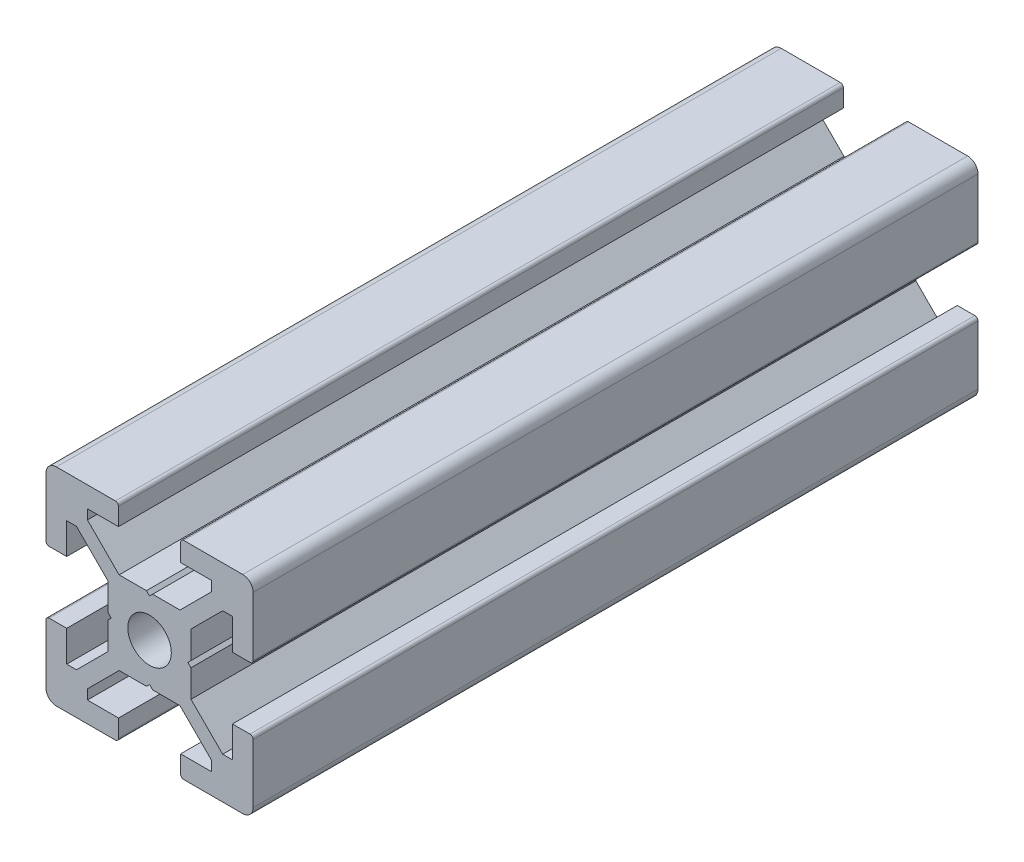
SolidWorks part; units mm, degrees
ref_plane "Front Plane" through (0, 0, 0) normal (0, 0, 1) x (1, 0, 0)
ref_plane "Top Plane" through (0, 0, 0) normal (0, 1, 0) x (1, 0, 0)
ref_plane "Right Plane" through (0, 0, 0) normal (1, 0, 0) x (0, 0, -1)
sketch "Sketch1" plane through (0, 0, 0) normal (0, 0, -1) x (-1, 0, 0)
  line L0 (10, 3.3) -> (10, 9)
  line L1 (9, 10) -> (3.3, 10)
  line L2 (3, 9.7) -> (3, 8)
  line L3 (3, 8) -> (6, 8)
  line L4 (6, 8) -> (6, 7.0607)
  line L5 (6, 7.0607) -> (2.9393, 4)
  line L6 (2.9393, 4) -> (0.3, 4)
  line L7 (0.3, 4) -> (0, 3.7)
  line L8 (0, 3.7) -> (-0.3, 4)
  line L9 (-0.3, 4) -> (-2.9393, 4)
  line L10 (-2.9393, 4) -> (-6, 7.0607)
  line L11 (-6, 7.0607) -> (-6, 8)
  line L12 (-6, 8) -> (-3, 8)
  line L13 (-3, 8) -> (-3, 9.7)
  line L14 (-3.3, 10) -> (-9, 10)
  line L15 (-10, 9) -> (-10, 3.3)
  line L16 (-9.7, 3) -> (-8, 3)
  line L17 (-8, 3) -> (-8, 6)
  line L18 (-8, 6) -> (-7.0607, 6)
  line L19 (-7.0607, 6) -> (-4, 2.9393)
  line L20 (-4, 2.9393) -> (-4, 0.3)
  line L21 (-4, 0.3) -> (-3.7, 0)
  line L22 (-3.7, 0) -> (-4, -0.3)
  line L23 (-4, -0.3) -> (-4, -2.9393)
  line L24 (-4, -2.9393) -> (-7.0607, -6)
  line L25 (-7.0607, -6) -> (-8, -6)
  line L26 (-8, -6) -> (-8, -3)
  line L27 (-8, -3) -> (-9.7, -3)
  line L28 (-10, -3.3) -> (-10, -9)
  line L29 (-9, -10) -> (-3.3, -10)
  line L30 (-3, -9.7) -> (-3, -8)
  line L31 (-3, -8) -> (-6, -8)
  line L32 (-6, -8) -> (-6, -7.0607)
  line L33 (-6, -7.0607) -> (-2.9393, -4)
  line L34 (-2.9393, -4) -> (-0.3, -4)
  line L35 (-0.3, -4) -> (0, -3.7)
  line L36 (0, -3.7) -> (0.3, -4)
  line L37 (0.3, -4) -> (2.9393, -4)
  line L38 (2.9393, -4) -> (6, -7.0607)
  line L39 (6, -7.0607) -> (6, -8)
  line L40 (6, -8) -> (3, -8)
  line L41 (3, -8) -> (3, -9.7)
  line L42 (3.3, -10) -> (9, -10)
  line L43 (10, -9) -> (10, -3.3)
  line L44 (9.7, -3) -> (8, -3)
  line L45 (8, -3) -> (8, -6)
  line L46 (8, -6) -> (7.0607, -6)
  line L47 (7.0607, -6) -> (4, -2.9393)
  line L48 (4, -2.9393) -> (4, -0.3)
  line L49 (4, -0.3) -> (3.7, 0)
  line L50 (3.7, 0) -> (4, 0.3)
  line L51 (4, 0.3) -> (4, 2.9393)
  line L52 (4, 2.9393) -> (7.0607, 6)
  line L53 (7.0607, 6) -> (8, 6)
  line L54 (8, 6) -> (8, 3)
  line L55 (8, 3) -> (9.7, 3)
  line L56 (9, -9) -> (-9, 9) construction
  line L57 (-9, -9) -> (9, 9) construction
  line L58 (-3.7, 0) -> (3.7, 0) construction
  line L59 (0, -3.7) -> (0, 3.7) construction
  circle A0 centre (0, 0) radius 2.1
  arc A1 (10, 9) -> (9, 10) centre (9, 9) ccw
  arc A2 (3.3, 10) -> (3, 9.7) centre (3.3, 9.7) ccw
  arc A3 (-3, 9.7) -> (-3.3, 10) centre (-3.3, 9.7) ccw
  arc A4 (-9, 10) -> (-10, 9) centre (-9, 9) ccw
  arc A5 (-10, 3.3) -> (-9.7, 3) centre (-9.7, 3.3) ccw
  arc A6 (-9.7, -3) -> (-10, -3.3) centre (-9.7, -3.3) ccw
  arc A7 (-10, -9) -> (-9, -10) centre (-9, -9) ccw
  arc A8 (-3.3, -10) -> (-3, -9.7) centre (-3.3, -9.7) ccw
  arc A9 (3, -9.7) -> (3.3, -10) centre (3.3, -9.7) ccw
  arc A10 (9, -10) -> (10, -9) centre (9, -9) ccw
  arc A11 (10, -3.3) -> (9.7, -3) centre (9.7, -3.3) ccw
  arc A12 (9.7, 3) -> (10, 3.3) centre (9.7, 3.3) ccw
  point P83 (0, 0)
  point P85 (0, 0)
  point P86 (0, 0)
  dimension "D1" = 1
  dimension "D4" = 0.3
  dimension "D10" = 4.2
  dimension "D2" = 20
  dimension "D3" = 6
  dimension "D5" = 3
  dimension "D6" = 1.7
  dimension "D7" = 0.9393
  dimension "D8" = 0.6
  dimension "D9" = 4
  dimension "D11" = 3.0607
  dimension "D12" = 3.0607
  dimension "D13" = 3.0607
  dimension "D14" = 5.7
  dimension "D15" = 5.7
  dimension "D16" = 0.9393
  dimension "D17" = 0.9393
  dimension "D18" = 3.0607
extrude "Boss-Extrude1" add sketch "Sketch1" against normal mid plane 70
ref_axis "Axis1" through (0, 0, 35) along (0, 0, -1)
